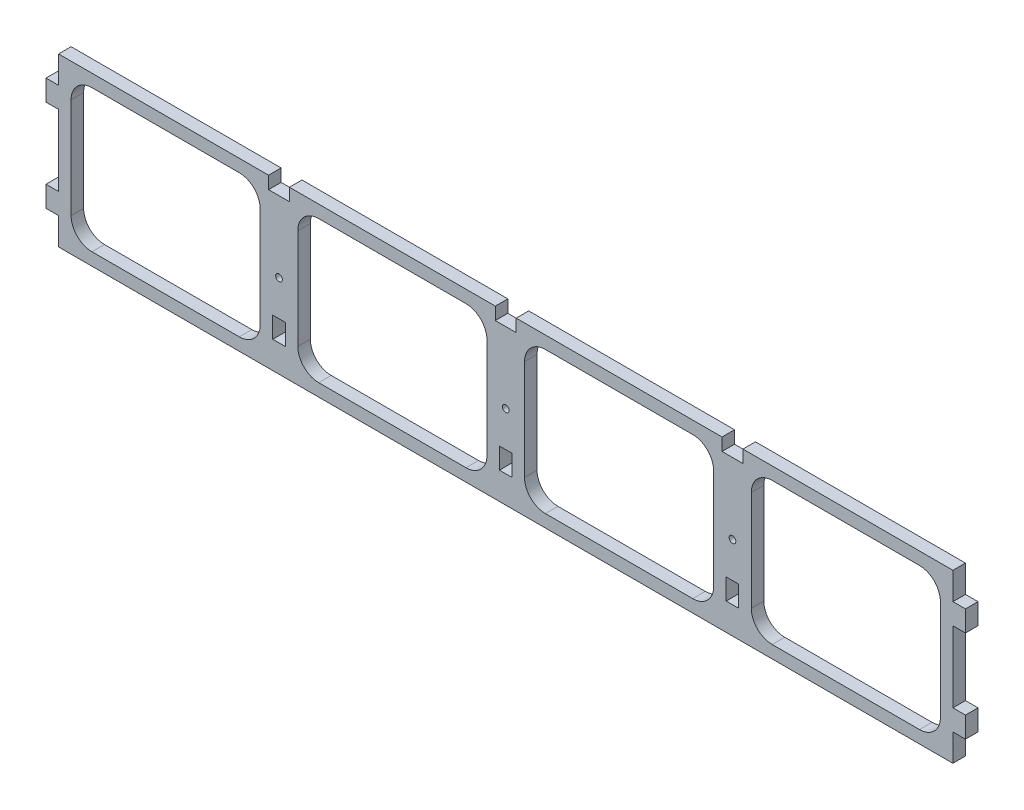
SolidWorks part; units mm, degrees
ref_plane "Front Plane" through (0, 0, 0) normal (0, 0, 1) x (1, 0, 0)
ref_plane "Top Plane" through (0, 0, 0) normal (0, 1, 0) x (1, 0, 0)
ref_plane "Right Plane" through (0, 0, 0) normal (1, 0, 0) x (0, 0, -1)
sketch "Sketch1" plane through (0, 0, 0) normal (0, 0, 1) x (1, 0, 0)
  line L1 (-214, -40) -> (214, -40)
  line L2 (-214, -40) -> (-214, 40)
  line L3 (-214, 40) -> (214, 40)
  line L4 (214, -40) -> (214, 40)
  line L5 (-214, -40) -> (214, 40) construction
  line L6 (-214, 40) -> (214, -40) construction
  point P0 (0, 0)
  dimension "D1" = 428
  dimension "D2" = 80
extrude "Boss-Extrude1" add sketch "Sketch1" along normal blind 6
sketch "Sketch2" plane through (0, 0, 6) normal (0, 0, 1) x (1, 0, 0)
  line L0 (-117.5, -40) -> (-117.5, -27) construction
  line L1 (-208, 40) -> (-208, -40) construction
  line L2 (-214, -34) -> (214, -34) construction
  line L3 (-214, -40) -> (214, -40) construction
  line L8 (214, -40) -> (214, 40)
  line L9 (214, 40) -> (-214, 40)
  line L10 (-214, 40) -> (-214, -40)
  line L11 (-214, -40) -> (214, -40)
  line L12 (214, -40) -> (214, 40) construction
  line L13 (214, 40) -> (-214, 40)
  line L14 (-214, 40) -> (-214, -40) construction
  line L15 (-208, -40) -> (214, -40) construction
  line L16 (-111.5, -40) -> (-111.5, -27) construction
  line L17 (-111.5, -40) -> (-111.5, -27) construction
  line L18 (-117.5, -24) -> (-117.5, 24)
  line L19 (-198, -34) -> (-127.5, -34)
  line L20 (-208, 24) -> (-208, -24)
  line L21 (-127.5, 34) -> (-198, 34)
  arc A0 (-198, 34) -> (-208, 24) centre (-198, 24) ccw
  arc A1 (-127.5, 34) -> (-117.5, 24) centre (-127.5, 24) cw
  arc A2 (-117.5, -24) -> (-127.5, -34) centre (-127.5, -24) cw
  arc A3 (-198, -34) -> (-208, -24) centre (-198, -24) cw
  dimension "D6" = 10
  dimension "D5" = 6
  dimension "D1" = 0
  dimension "D2" = 6
  dimension "D3" = 6
  dimension "D4" = 6
extrude "Cut-Extrude1" cut sketch "Sketch2" against normal up to next contours L18 L21 L20 L19 region at (-162.75, 0, 6)
pattern_linear "LPattern1" count 4 spacing 108.5 along (1, 0, 0) of "Cut-Extrude1"
sketch "Sketch3" plane through (0, 0, 0) normal (0, 0, -1) x (-1, 0, 0)
  line L8 (-111.5, -27) -> (-111.5, -17) construction
  line L9 (-111.5, -17) -> (-105.5, -17) construction
  line L10 (-105.5, -17) -> (-105.5, -27) construction
  line L11 (-105.5, -27) -> (-111.5, -27) construction
  line L24 (-111.5, -27) -> (-111.5, -17)
  line L25 (-111.5, -17) -> (-105.5, -17)
  line L26 (-105.5, -17) -> (-105.5, -27)
  line L27 (-105.5, -27) -> (-111.5, -27)
  line L44 (-3, -27) -> (-3, -17) construction
  line L45 (-3, -17) -> (3, -17) construction
  line L46 (3, -17) -> (3, -27) construction
  line L47 (3, -27) -> (-3, -27) construction
  line L52 (-3, -27) -> (-3, -17)
  line L53 (-3, -17) -> (3, -17)
  line L54 (3, -17) -> (3, -27)
  line L55 (3, -27) -> (-3, -27)
  line L60 (105.5, -27) -> (105.5, -17) construction
  line L61 (105.5, -17) -> (111.5, -17) construction
  line L62 (111.5, -17) -> (111.5, -27) construction
  line L63 (111.5, -27) -> (105.5, -27) construction
  line L68 (105.5, -27) -> (105.5, -17)
  line L69 (105.5, -17) -> (111.5, -17)
  line L70 (111.5, -17) -> (111.5, -27)
  line L71 (111.5, -27) -> (105.5, -27)
  circle A3 centre (108.5, 0) radius 1.6 construction
  circle A4 centre (0, 0) radius 1.6 construction
  circle A5 centre (-108.5, 0) radius 1.6 construction
  circle A6 centre (108.5, 0) radius 1.6
  circle A7 centre (0, 0) radius 1.6
  circle A8 centre (-108.5, 0) radius 1.6
extrude "Cut-Extrude2" cut sketch "Sketch3" against normal through all
sketch "Sketch4" plane through (0, 0, 0) normal (0, 0, -1) x (-1, 0, 0)
  line L0 (-111.5, 17) -> (-214, 17) construction
  line L1 (-214, -40) -> (-214, 40) construction
  line L2 (-108.5, 0) -> (-214, 0) construction
  line L3 (-220, 21.3321) -> (-220, 40) construction
  line L4 (-214, 17) -> (-220, 17)
  line L5 (-214, 17) -> (-214, 27)
  line L6 (-214, 27) -> (-220, 27)
  line L7 (-220, 17) -> (-220, 27)
  line L9 (-220, -17) -> (-220, -27)
  line L10 (-214, -27) -> (-220, -27)
  line L11 (-214, -17) -> (-214, -27)
  line L12 (-214, -17) -> (-220, -17)
  line L13 (0, 0) -> (0, 40) construction
  line L14 (-214, 40) -> (214, 40) construction
  line L15 (214, -17) -> (220, -17)
  line L16 (214, -17) -> (214, -27)
  line L17 (214, -27) -> (220, -27)
  line L18 (220, -17) -> (220, -27)
  line L19 (220, 17) -> (220, 27)
  line L20 (214, 27) -> (220, 27)
  line L21 (214, 17) -> (214, 27)
  line L22 (214, 17) -> (220, 17)
  dimension "D1" = 34
  dimension "D2" = 10
extrude "Boss-Extrude2" add sketch "Sketch4" against normal blind 6
sketch "Sketch5" plane through (0, 40, 0) normal (0, 1, 0) x (1, 0, 0)
  line L0 (214, -6) -> (-214, -6) construction
  line L1 (-113.5, 0) -> (-103.5, 0)
  line L2 (-113.5, 0) -> (-113.5, -6)
  line L3 (-113.5, -6) -> (-103.5, -6)
  line L4 (-103.5, 0) -> (-103.5, -6)
  line L5 (-113.5, 0) -> (-103.5, -6) construction
  line L6 (-113.5, -6) -> (-103.5, 0) construction
  line L7 (-103.5, -6) -> (-103.5, 0) construction
  line L8 (5, -6) -> (5, 0) construction
  line L9 (-5, 0) -> (5, 0)
  line L10 (-5, 0) -> (-5, -6)
  line L11 (-5, -6) -> (5, -6)
  line L12 (5, 0) -> (5, -6)
  line L13 (-5, 0) -> (5, -6) construction
  line L14 (-5, -6) -> (5, 0) construction
  line L15 (113.5, -6) -> (113.5, 0) construction
  line L16 (103.5, 0) -> (113.5, 0)
  line L17 (103.5, 0) -> (103.5, -6)
  line L18 (103.5, -6) -> (113.5, -6)
  line L19 (113.5, 0) -> (113.5, -6)
  line L20 (103.5, 0) -> (113.5, -6) construction
  line L21 (103.5, -6) -> (113.5, 0) construction
  point P0 (-108.5, -3)
  point P10 (0, -3)
  point P18 (108.5, -3)
extrude "Cut-Extrude3" cut sketch "Sketch5" against normal blind 6
